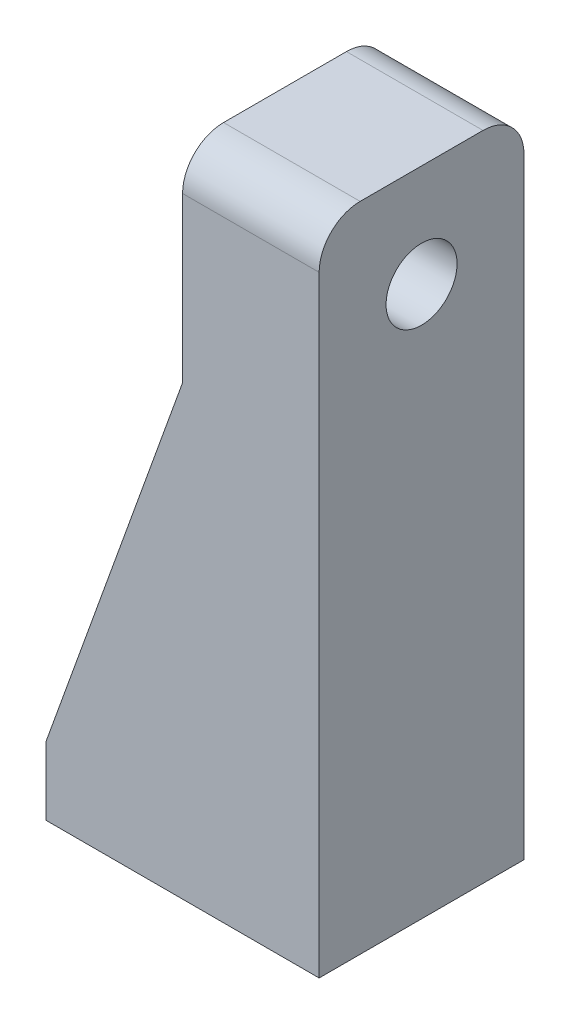
SolidWorks part; units mm, degrees
ref_plane "前视基准面" through (0, 0, 0) normal (0, 0, 1) x (1, 0, 0)
ref_plane "上视基准面" through (0, 0, 0) normal (0, 1, 0) x (1, 0, 0)
ref_plane "右视基准面" through (0, 0, 0) normal (1, 0, 0) x (0, 0, -1)
other "Configuration Table"
sketch "草图1" plane through (0, 0, 0) normal (0, 0, 1) x (1, 0, 0)
  line L0 (0, 0) -> (0, 42.75)
  line L1 (0, 42.75) -> (-10, 42.75)
  line L2 (-10, 42.75) -> (-10, 27.75)
  line L3 (-10, 27.75) -> (-20, 0)
  line L4 (-20, 0) -> (0, 0)
  line L6 (-20, 0) -> (0, 0)
  line L7 (-20, 0) -> (-20, -5)
  line L8 (-20, -5) -> (0, -5)
  line L9 (0, 0) -> (0, -5)
  point P8 (-10, 35.25)
  dimension "D1" = 40.25
  dimension "D2" = 15
  dimension "D3" = 10
  dimension "D4" = 20
  dimension "D5" = 5
extrude "凸台-拉伸1" add sketch "草图1" along normal blind 15 contours L3 L4 L0 L1 L2 | L9 L4 L7 L8 region at (-7.0419, 18.404, 0) region at (-10, -2.5, 0)
sketch "草图2" plane through (-10, 0, 0) normal (-1, 0, 0) x (0, 0, 1)
  line L0 (0, 42.75) -> (15, 27.75) construction
  circle A0 centre (7.5, 35.25) radius 2
  dimension "D1" = 4
fillet "圆角1" radius 3 2 edges at (-5, 42.75, 15) (-5, 42.75, 0)
sketch "草图3" plane through (0, 0, 0) normal (1, 0, 0) x (0, 0, -1)
  circle A0 centre (-7.5, 35.25) radius 2.6
  dimension "D1" = 5.2
extrude "切除-拉伸1" cut sketch "草图3" against normal through all
sketch "草图6" plane through (0, 0, 8) normal (0, 0, 1) x (1, 0, 0)
  line L0 (0, -5) -> (0, 39.75) construction
  line L2 (38, 0) -> (38, 44.842) construction
  dimension "D1" = 38
ref_plane "基准面1" through (0, 0, 7.5) normal (0, 0, 1) x (1, 0, 0)
sketch "草图8" plane through (0, 0, 7.5) normal (0, 0, 1) x (1, 0, 0)
  line L0 (38, 0) -> (38, 44.842) construction
  line L1 (38, 0) -> (38, 44.842) construction
  line L2 (0, 2) -> (-6, 2)
  line L3 (0, 0) -> (0, 37.25) construction
  line L4 (-6, 2) -> (-6, -5)
  line L6 (-6, -5) -> (-2, -5)
  line L7 (-2, -5) -> (-2, 0)
  line L8 (-2, 0) -> (0, 0)
  line L9 (0, 0) -> (0, 2)
  line L10 (0, -5) -> (0, 39.75) construction
  line L11 (-20, -5) -> (0, -5) construction
  dimension "D1" = 4
  dimension "D2" = 0
  dimension "D3" = 2
  dimension "D4" = 2
  dimension "D5" = 0
  dimension "D6" = 5
sketch "草图9" plane through (-10, 0, 0) normal (-1, 0, 0) x (0, 0, 1)
  circle A0 centre (7.5, 35.25) radius 3.5
  circle A1 centre (7.5, 35.25) radius 4.5
  dimension "D1" = 7
  dimension "D2" = 9
extrude "切除-拉伸2" cut sketch "草图9" against normal blind 2
fillet "圆角2" radius 1 1 edges at (-10, 37.85, 7.5)
